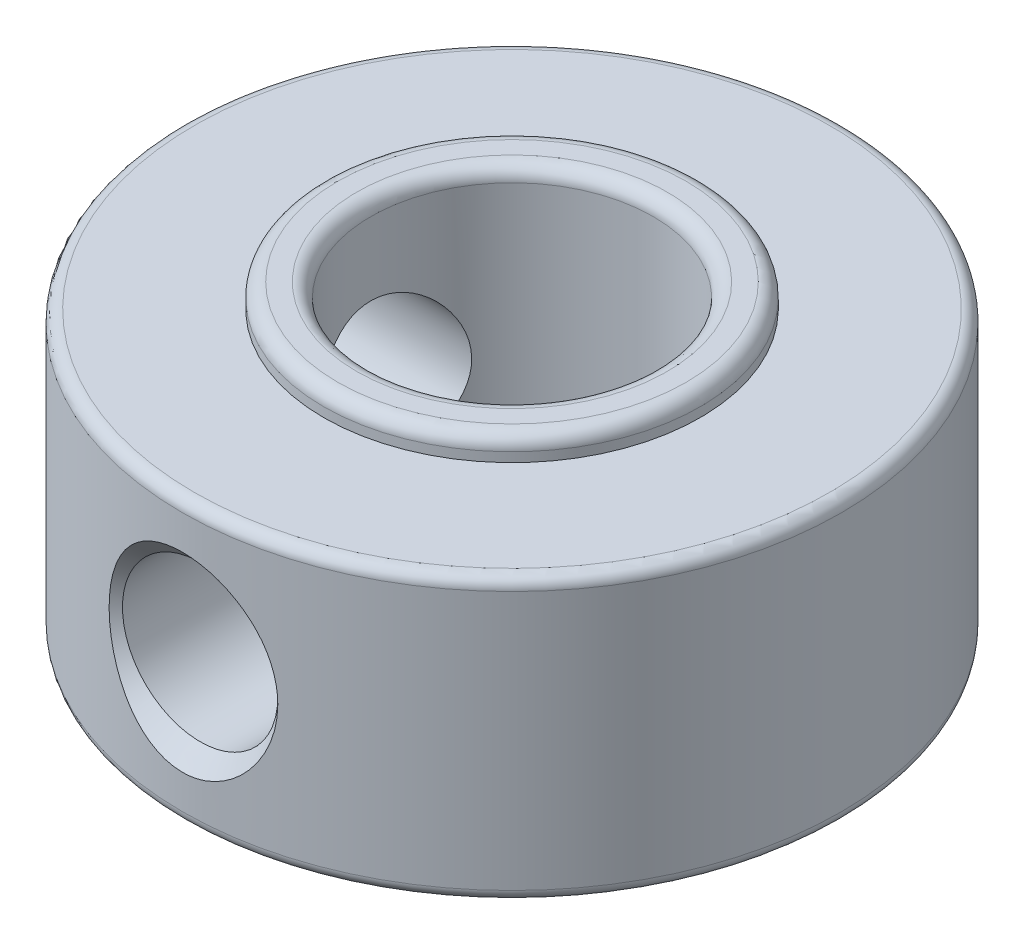
SolidWorks part; units mm, degrees
material "6061-T6 (SS)"
ref_plane "Front Plane" through (0, 0, 0) normal (0, 0, 1) x (1, 0, 0)
ref_plane "Top Plane" through (0, 0, 0) normal (0, 1, 0) x (1, 0, 0)
ref_plane "Right Plane" through (0, 0, 0) normal (1, 0, 0) x (0, 0, -1)
sketch "Sketch1" plane through (0, 0, 0) normal (0, 1, 0) x (1, 0, 0)
  circle A0 centre (0, 0) radius 7
  circle A1 centre (0, 0) radius 3
  dimension "D1" = 14
  dimension "D2" = 6
extrude "Boss-Extrude1" add sketch "Sketch1" along normal blind 6
sketch "Sketch2" plane through (0, 6, 0) normal (0, 1, 0) x (1, 0, 0)
  circle A0 centre (0, 0) radius 4
  circle A1 centre (0, 0) radius 3
  dimension "D1" = 8
extrude "Boss-Extrude2" add sketch "Sketch2" along normal blind 0.5
fillet "Fillet1" radius 0.3 2 edges at (0, 6.5, 3) (0, 6.5, 4)
fillet "Fillet2" radius 0.25 2 edges at (0, 0, 7) (0, 6, 7)
ref_plane "Plane1" through (0, 0, 7) normal (0, 0, 1) x (1, 0, 0)
sketch "Sketch3" plane through (0, 0, 7) normal (0, 0, 1) x (1, 0, 0)
  line L0 (0, -3.575) -> (0, 3.575) construction
  point P0 (0, 3)
  dimension "D1" = 3
hole_wizard "M4 Tapped Hole1" positions "Sketch6" profile "Sketch5" tap size "M4" standard "ISO" end condition up to next
sketch "Sketch6" plane through (0, 0, 7) normal (0, 0, 1) x (1, 0, 0)
  point P0 (0, 3)
sketch "Sketch5" plane through (0, 3, 7) normal (1, 0, 0) x (0, -1, 0)
  line L0 (0, 0) -> (0, 14)
  line L1 (0, 14) -> (1.65, 14)
  line L2 (1.65, 14) -> (1.65, 0.375)
  line L3 (1.65, 0.375) -> (2.025, 0)
  line L5 (2.025, 0) -> (0, 0)
  line L6 (-1.65, 0.375) -> (-2.025, 0) construction
  line L11 (0, -6.35) -> (0, 107.95) construction
  dimension "Thru Tap Drill Dia." = 3.3
  dimension "Thru Tap Drill Depth" = 14
  dimension "Near C'Sink Dia." = 4.05
  dimension "Near C'Sink Angle" = 90
cosmetic thread "Hole Thread1" parameters "D2"=4
pattern_circular "CirPattern1" count 2 over 90 about axis through (0, 6, 0) along (0, -1, 0) of "M4 Tapped Hole1"
